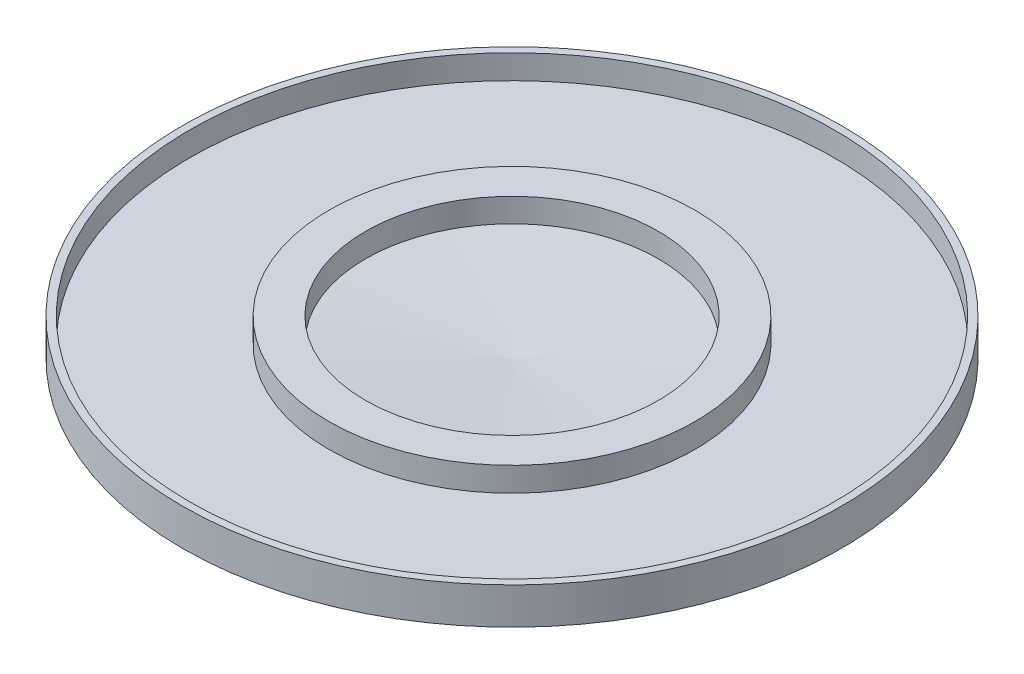
SolidWorks part; units mm, degrees
ref_plane "前视基准面" through (0, 0, 0) normal (0, 0, 1) x (1, 0, 0)
ref_plane "上视基准面" through (0, 0, 0) normal (0, 1, 0) x (1, 0, 0)
ref_plane "右视基准面" through (0, 0, 0) normal (1, 0, 0) x (0, 0, -1)
sketch "草图1" plane through (0, 0, 0) normal (0, 0, 1) x (1, 0, 0)
  line L0 (0, 0) -> (200, 17.4992)
  line L1 (0, 0) -> (200, 0)
  line L2 (200, 0) -> (200, 17.4992)
sketch "草图4" plane through (0, 0, 0) normal (0, 0, 1) x (1, 0, 0)
  line L0 (-0.01, 0) -> (-0.01, 2.109)
sketch "草图6" plane through (0, 0, 0) normal (0, 1, 0) x (1, 0, 0)
  circle A0 centre (-0.01, 0) radius 0.01
revolve "旋转1" add sketch "草图1" angle 360 about L0
sketch "草图8" plane through (0, 0, 0) normal (0, 1, 0) x (1, 0, 0)
  circle A0 centre (0, 0) radius 200.02
  circle A1 centre (0, 0) radius 250
  circle A2 centre (0, 0) radius 450
  circle A3 centre (0, 0) radius 440
extrude "凸台-拉伸1" add sketch "草图8" along normal blind 50 separate body contours A1 A0 | A2 A3 region at (-242.9289, 0, 0) region at (-448.7272, 0, 0)
extrude "凸台-拉伸2" add sketch "草图8<3>" along normal blind 17 contours A3 A1 region at (-427.5549, 0, 0)
sketch "草图8<3>" plane through (0, 0, 0) normal (0, 1, 0) x (1, 0, 0) same geometry as "草图8"
sketch "草图3" plane through (0, 0, 0) normal (1, 0, 0) x (0, 0, -1)
  line L0 (0, 0) -> (0.0019, 0)
  line L1 (0.0019, 0) -> (-0.002, 0)
